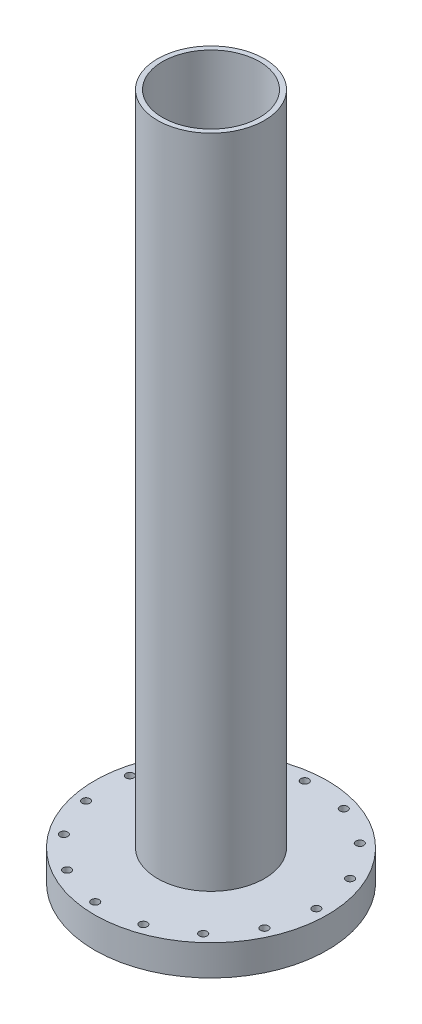
SolidWorks part; units mm, degrees
ref_plane "Front Plane" through (0, 0, 0) normal (0, 0, 1) x (1, 0, 0)
ref_plane "Top Plane" through (0, 0, 0) normal (0, 1, 0) x (1, 0, 0)
ref_plane "Right Plane" through (0, 0, 0) normal (1, 0, 0) x (0, 0, -1)
sketch "Sketch1" plane through (0, 0, 0) normal (0, 1, 0) x (1, 0, 0)
  circle A0 centre (0, 0) radius 31.75
  circle A1 centre (0, 0) radius 35
  dimension "D1" = 63.5
  dimension "D2" = 70
extrude "Boss-Extrude1" add sketch "Sketch1" along normal blind 450
sketch "Sketch2" plane through (0, 0, 0) normal (0, 1, 0) x (1, 0, 0)
  circle A0 centre (0, 0) radius 76.2
  circle A1 centre (0, 0) radius 31.75
  circle A2 centre (0, 0) radius 31.75 construction
  dimension "D1" = 152.4
extrude "Boss-Extrude2" add sketch "Sketch2" along normal blind 20 separate body
hole_wizard "13/64 (0.20313) Diameter Hole1" positions "Sketch4" profile "Sketch5" hole size "13/64" standard "ANSI Inch" end condition through all
sketch "Sketch4" plane through (0, 0, 0) normal (0, -1, 0) x (-1, 0, 0)
  point P0 (-69, 0)
  point P4 (0, 0)
  dimension "D1" = 69
sketch "Sketch5" plane through (69, 0, 0) normal (1, 0, 0) x (0, 0, -1)
  line L0 (0, 0) -> (0, 450)
  line L1 (0, 450) -> (2.5798, 450)
  line L2 (2.5798, 450) -> (2.5798, 0)
  line L5 (2.5798, 0) -> (0, 0)
  line L11 (0, -6.35) -> (0, 107.95) construction
  dimension "Thru Hole Dia." = 5.1595
  dimension "Thru Hole Depth" = 450
ref_axis "Axis1" through (0, 472.5, 0) along (0, -1, 0)
pattern_circular "CirPattern1" count 15 over 360 about axis through (0, 472.5, 0) along (0, -1, 0) of "13/64 (0.20313) Diameter Hole1"
sketch "Sketch6" plane through (0, 0, 0) normal (0, -1, 0) x (1, 0, 0)
  circle A0 centre (0, 0) radius 55.14 construction
  circle A1 centre (0, 0) radius 55.14
extrude "Cut-Extrude1" cut sketch "Sketch6" against normal blind 2
